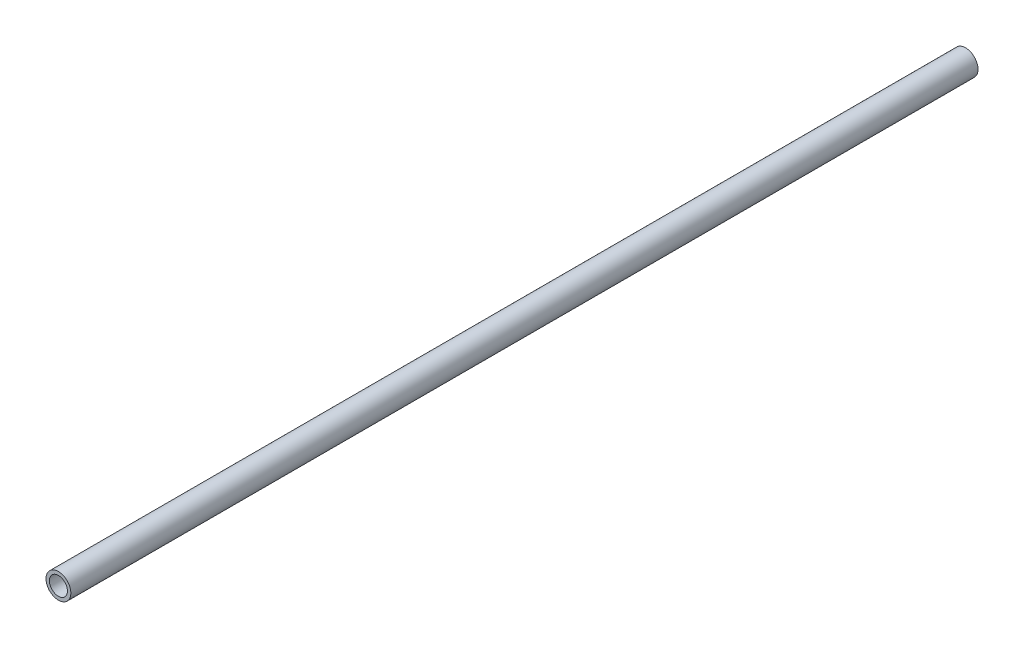
SolidWorks part; units mm, degrees
ref_plane "Front Plane" through (0, 0, 0) normal (0, 0, 1) x (1, 0, 0)
ref_plane "Top Plane" through (0, 0, 0) normal (0, 1, 0) x (1, 0, 0)
ref_plane "Right Plane" through (0, 0, 0) normal (1, 0, 0) x (0, 0, -1)
sketch "Sketch1" plane through (0, 0, 0) normal (0, 0, 1) x (1, 0, 0)
  circle A0 centre (0, 0) radius 16.7005
  dimension "Pipe OD" = 33.401
extrude "Extrude-Thin1" add sketch "Sketch1" along normal mid plane 1219.2 thin thin type one direction reverse wall 4.5466
